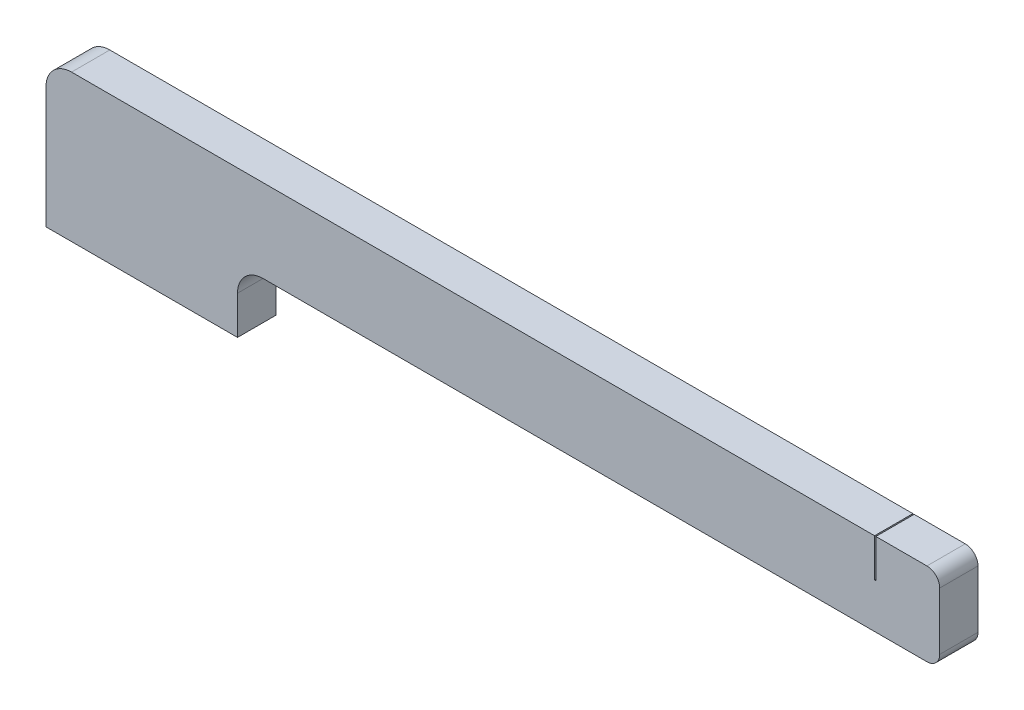
SolidWorks part; units mm, degrees
ref_plane "Front Plane" through (0, 0, 0) normal (0, 0, 1) x (1, 0, 0)
ref_plane "Top Plane" through (0, 0, 0) normal (0, 1, 0) x (1, 0, 0)
ref_plane "Right Plane" through (0, 0, 0) normal (1, 0, 0) x (0, 0, -1)
sketch "Sketch1" plane through (0, 0, 0) normal (0, 0, 1) x (1, 0, 0)
  line L0 (0, 0) -> (0, 9.5)
  line L1 (2, 11.5) -> (69, 11.5)
  line L2 (70, 10.5) -> (70, 6)
  line L3 (69, 5) -> (17, 5)
  line L4 (15, 3) -> (15, 0)
  line L5 (15, 0) -> (0, 0)
  arc A0 (17, 5) -> (15, 3) centre (17, 3) ccw
  arc A1 (2, 11.5) -> (0, 9.5) centre (2, 9.5) ccw
  arc A2 (70, 10.5) -> (69, 11.5) centre (69, 10.5) ccw
  arc A3 (69, 5) -> (70, 6) centre (69, 6) ccw
  point P11 (0, 11.5)
  point P14 (70, 11.5)
  point P17 (70, 5)
  dimension "D5" = 2
  dimension "D6" = 2
  dimension "D7" = 1
  dimension "D2" = 15
  dimension "D3" = 6.5
  dimension "D4" = 70
extrude "Boss-Extrude1" add sketch "Sketch1" along normal blind 3
sketch "Sketch3" plane through (0, 11.5, 0) normal (0, 1, 0) x (1, 0, 0)
  line L0 (0, -1.5) -> (64.95, -1.5) construction
  line L1 (0, -3) -> (0, 0) construction
  line L2 (69, 0) -> (2, 0) construction
  line L3 (64.9, -3) -> (65, -3)
  line L4 (64.9, -3) -> (64.9, 0)
  line L5 (64.9, 0) -> (65, 0)
  line L6 (65, -3) -> (65, 0)
  line L7 (64.9, -3) -> (65, 0) construction
  line L8 (64.9, 0) -> (65, -3) construction
  dimension "D1" = 64.95
extrude "Cut-Extrude1" cut sketch "Sketch3" against normal blind 3
equation "\"A.L\"= 0.07m"
equation "\"A.h\"= 0.007m"
equation "\"A.d\"= 0.003m"
equation "\"A.delta\"= 45.0001"
equation "\"A.w\"= 0.02m"
equation "\"A.v\"= 0.03m"
equation "\"A.s\"= 0.014m"
equation "\"A.t\"= 0.007m"
equation "\"B.L\"= 0.065m"
equation "\"B.h\"= 0.008m"
equation "\"B.s\"= 0.016m"
equation "\"B.t\"= 0.008m"
equation "\"C.h\"= 0.0065m"
equation "\"C.d\"= 0.003m"
equation "\"C.L\"= 0.05m"
equation "\"C.wmax\"= 0.005m"
equation "\"D.L\"= 0.06m"
equation "\"D.h\"= 0.008m"
equation "\"D.s\"= 0.012m"
equation "\"D.t\"= 0.008m"
equation "\"a_h\"= 0.0002m"
equation "\"a_d\"= 0.003m"
equation "\"a_L\"= 0.008m"
equation "\"b_h\"= 0.0004m"
equation "\"b_d\"= 0.003m"
equation "\"b_L\"= 0.007m"
equation "\"c_h\"= 0.0001m"
equation "\"c_d\"= 0.003m"
equation "\"c_L\"= 0.01m"
equation "\"d_h\"= 0.0001m"
equation "\"d_d\"= 0.003m"
equation "\"d_L\"= 0.01m"
equation "\"S.h\"= 0.015m"
equation "\"S.L\"= 0.09075m"
equation "\"D1@Sketch1\"=\"C.h\"+\"C.wmax\""
equation "\"D2@Sketch1\"=\"S.h\""
equation "\"D3@Sketch1\"=\"C.h\""
equation "\"D4@Sketch1\"=\"C.L\"+\"S.h\"+0.005"
equation "\"D1@Boss-Extrude1\"=\"C.d\""
equation "\"D1@Sketch3\"=\"C.L\"+\"S.h\"-\"c_h\"/2"
equation "\"D2@Sketch3\"=\"c_h\""
